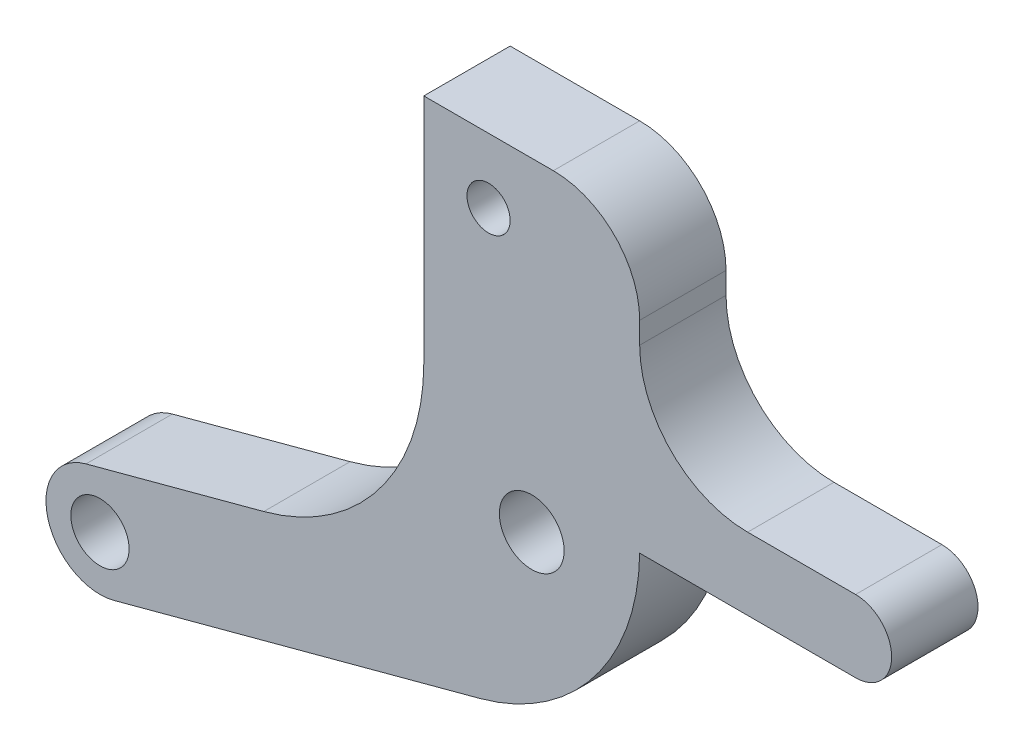
SolidWorks part; units mm, degrees
ref_plane "Front Plane" through (0, 0, 0) normal (0, 0, 1) x (1, 0, 0)
ref_plane "Top Plane" through (0, 0, 0) normal (0, 1, 0) x (1, 0, 0)
ref_plane "Right Plane" through (0, 0, 0) normal (1, 0, 0) x (0, 0, -1)
sketch "Sketch1" plane through (0, 0, 0) normal (0, 0, 1) x (1, 0, 0)
  line L0 (0, 0) -> (4.4859, -8.4734) construction
  line L1 (-31.326, -6.6342) -> (8.674, -6.6342) construction
  line L2 (-31.326, -6.6342) -> (-31.326, 38.3658) construction
  line L3 (-31.326, 38.3658) -> (8.674, 38.3658) construction
  line L4 (8.674, -6.6342) -> (8.674, 38.3658) construction
  line L6 (15, 5) -> (5, 5)
  line L7 (5, 5) -> (5, 15)
  line L8 (5, 15) -> (-5, 15)
  line L9 (-5, 15) -> (-5, -3.3926)
  line L10 (-5, -3.3926) -> (-20.647, -7.5852)
  line L11 (5, -5.8895) -> (5, 1.6588)
  line L12 (-19.353, -12.4148) -> (5, -5.8895)
  line L13 (5, 1.6588) -> (15, 1.6588)
  circle A0 centre (0, 0) radius 1.5
  arc A1 (-20.647, -7.5852) -> (-19.353, -12.4148) centre (-20, -10) ccw
  circle A2 centre (-2, 12) radius 1
  arc A3 (15, 5) -> (15, 1.6588) centre (15, 3.3294) cw
  circle A4 centre (-20, -10) radius 1.35
  dimension "D5" = 2.5
  dimension "D9" = 2
  dimension "D10" = 3
  dimension "D15" = 2.7
  dimension "D1" = 40
  dimension "D2" = 45
  dimension "D3" = 105
  dimension "D4" = 5
  dimension "D6" = 10
  dimension "D7" = 15
  dimension "D8" = 5
  dimension "D11" = 2
  dimension "D12" = 12
  dimension "D13" = 20
  dimension "D14" = 10
  dimension "D16" = 15
extrude "Boss-Extrude1" add sketch "Sketch1" along normal blind 4
fillet "Fillet1" radius 10 1 edges at (5, -5.8895, 2)
fillet "Fillet2" radius 10 1 edges at (-5, -3.3926, 2)
fillet "Fillet3" radius 5 1 edges at (5, 5, 2)
fillet "Fillet4" radius 4 1 edges at (5, 15, 2)
